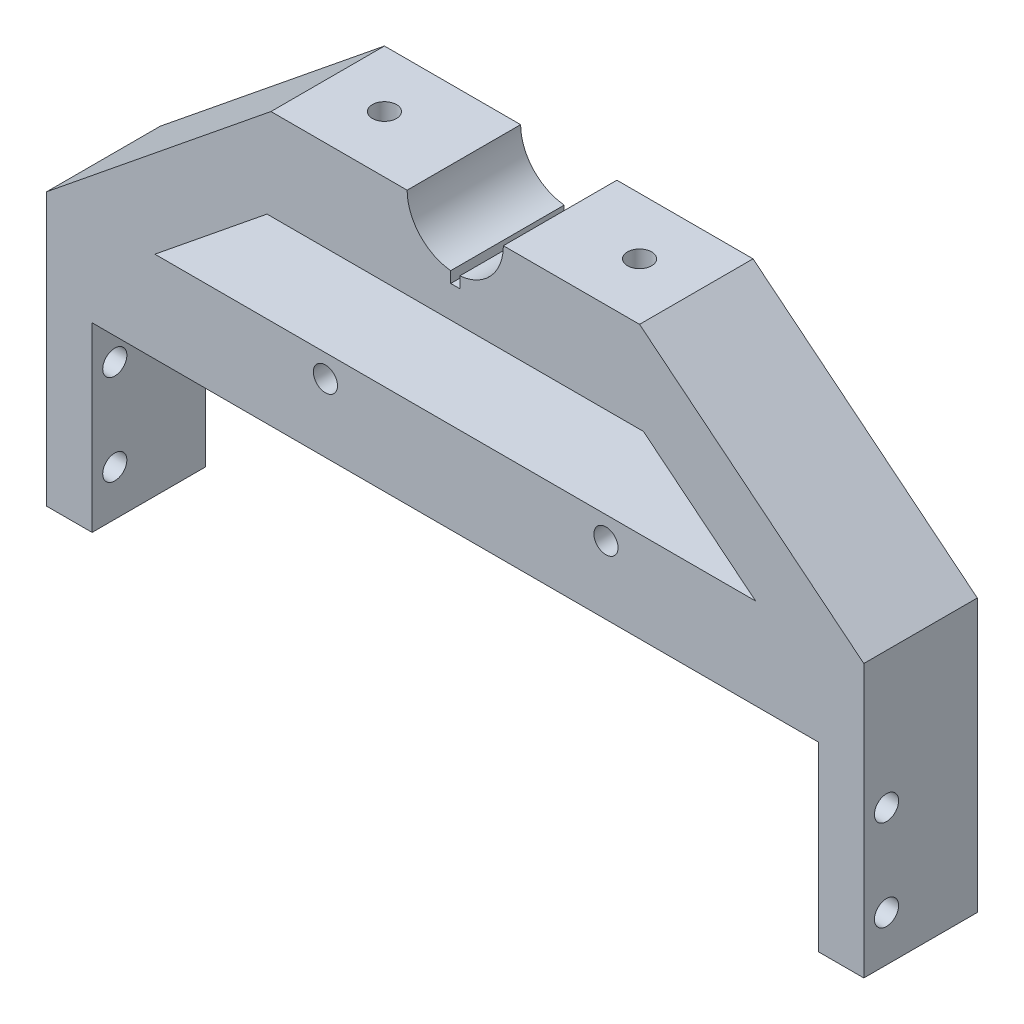
SolidWorks part; units mm, degrees
ref_plane "Front Plane" through (0, 0, 0) normal (0, 0, 1) x (1, 0, 0)
ref_plane "Top Plane" through (0, 0, 0) normal (0, 1, 0) x (1, 0, 0)
ref_plane "Right Plane" through (0, 0, 0) normal (1, 0, 0) x (0, 0, -1)
sketch "Sketch2" plane through (0, 0, 0) normal (0, 0, 1) x (1, 0, 0)
  line L0 (254, 0) -> (266.7, 0)
  line L4 (266.7, 0) -> (266.7, 101.6)
  line L9 (50.8, 0) -> (38.1, 0)
  line L10 (38.1, 0) -> (38.1, 101.6)
  line L12 (38.1, 101.6) -> (100.838, 152.4)
  line L13 (266.7, 101.6) -> (203.962, 152.4)
  line L14 (100.838, 152.4) -> (138.938, 152.4)
  line L15 (165.862, 152.4) -> (203.962, 152.4)
  line L16 (50.8, 0) -> (50.8, 76.2)
  line L17 (50.8, 76.2) -> (254, 76.2)
  line L18 (254, 76.2) -> (254, 0)
  arc A3 (138.938, 152.4) -> (165.862, 152.4) centre (152.4, 152.4) ccw
  dimension "D3" = 12.7
  dimension "D7" = 13.462
  dimension "D2" = 12.7
  dimension "D4" = 228.6
  dimension "D5" = 38.1
  dimension "D8" = 114.3
  dimension "D9" = 38.1
  dimension "D10" = 101.6
  dimension "D11" = 50.8
  dimension "D12" = 76.2
  dimension "D13" = 101.6
  dimension "D14" = 203.2
extrude "Boss-Extrude1" add sketch "Sketch2" along normal blind 50.8
sketch "Sketch3" plane through (38.1, 0, 0) normal (-1, 0, 0) x (0, 0, 1)
  line L2 (50.8, 0) -> (0, 0) construction
  circle A0 centre (25.4, 63.5) radius 3.3782
  circle A1 centre (25.4, 38.1) radius 3.3782
  dimension "D1" = 6.7564
  dimension "D2" = 6.7564
  dimension "D3" = 38.1
  dimension "D4" = 25.4
extrude "Cut-Extrude1" cut sketch "Sketch3" against normal blind 25.4
sketch "Sketch4" plane through (266.7, 0, 0) normal (1, 0, 0) x (0, 0, -1)
  line L1 (-50.8, 0) -> (0, 0) construction
  circle A0 centre (-25.4, 63.5) radius 3.3782
  circle A1 centre (-25.4, 38.1) radius 3.3782
  dimension "D1" = 6.7564
  dimension "D2" = 6.7564
  dimension "D5" = 38.1
  dimension "D6" = 63.5
extrude "Cut-Extrude2" cut sketch "Sketch4" against normal blind 25.4
sketch "Sketch7" plane through (0, 0, 50.8) normal (0, 0, 1) x (1, 0, 0)
  line L1 (12.1672, -21.2745) -> (291.9081, -21.2745)
  line L2 (12.1672, -21.2745) -> (12.1672, 173.6745)
  line L3 (12.1672, 173.6745) -> (291.9081, 173.6745)
  line L4 (291.9081, -21.2745) -> (291.9081, 173.6745)
extrude "Cut-Extrude5" cut sketch "Sketch7" against normal blind 19.05
sketch "Sketch8" plane through (0, 0, 31.75) normal (0, 0, 1) x (1, 0, 0)
  line L0 (38.1, 0) -> (38.1, 101.6) construction
  line L1 (38.1, 25.4) -> (266.7, 25.4)
  line L2 (38.1, 25.4) -> (38.1, 0)
  line L3 (38.1, 0) -> (266.7, 0)
  line L4 (266.7, 25.4) -> (266.7, 0)
  dimension "D1" = 25.4
extrude "Cut-Extrude6" cut sketch "Sketch8" against normal blind 39.37
sketch "Sketch9" plane through (0, 152.4, 0) normal (0, 1, 0) x (1, 0, 0)
  line L1 (138.938, 0) -> (100.838, 0) construction
  line L2 (203.962, 0) -> (165.862, 0) construction
  line L4 (100.838, -31.75) -> (100.838, 0) construction
  line L5 (203.962, -31.75) -> (203.962, 0) construction
  circle A0 centre (116.713, -15.875) radius 3.3782
  circle A1 centre (188.087, -15.875) radius 3.3782
  dimension "D1" = 6.7564
  dimension "D2" = 6.7564
  dimension "D3" = 15.875
  dimension "D4" = 15.875
  dimension "D5" = 15.875
  dimension "D6" = 15.875
extrude "Cut-Extrude7" cut sketch "Sketch9" against normal blind 27.94
sketch "Sketch10" plane through (0, 0, 31.75) normal (0, 0, 1) x (1, 0, 0)
  line L7 (68.3723, 101.6) -> (99.7413, 127)
  line L8 (99.7413, 127) -> (205.0587, 127)
  line L9 (68.3723, 101.6) -> (236.4277, 101.6)
  line L10 (38.1, 101.6) -> (100.838, 152.4) construction
  line L11 (205.0587, 127) -> (236.4277, 101.6)
  line L12 (203.962, 152.4) -> (266.7, 101.6) construction
  dimension "D1" = 25.4
  dimension "D2" = 19.05
  dimension "D3" = 19.05
extrude "Cut-Extrude8" cut sketch "Sketch10" against normal blind 40.64
sketch "Sketch12" plane through (0, 152.4, 0) normal (0, 1, 0) x (1, 0, 0)
  line L0 (152.4, -31.75) -> (152.4, 0)
  line L1 (138.938, -31.75) -> (165.862, -31.75) construction
  line L2 (165.862, 0) -> (138.938, 0) construction
  line L3 (152.4, 0) -> (153.67, 0)
  line L4 (153.67, 0) -> (153.67, -31.75)
  line L5 (153.67, -31.75) -> (151.13, -31.75)
  line L6 (151.13, -31.75) -> (151.13, 0)
  line L7 (151.13, 0) -> (152.4, 0)
  dimension "D1" = 1.27
  dimension "D2" = 1.27
extrude "Cut-Extrude9" cut sketch "Sketch12" against normal blind 16.51 contours L5 L4 L3 L0 | L7 L6 L5 L0 region at (151.765, 152.4, 15.875) region at (153.035, 152.4, 15.875)
sketch "Sketch13" plane through (0, 0, 31.75) normal (0, 0, 1) x (1, 0, 0)
  line L1 (68.3723, 101.6) -> (236.4277, 101.6) construction
  line L2 (38.1, 25.4) -> (38.1, 101.6) construction
  circle A0 centre (116.078, 95.25) radius 3.3782
  circle A1 centre (194.564, 95.25) radius 3.3782
  dimension "D1" = 6.7564
  dimension "D2" = 6.7564
  dimension "D3" = 6.35
  dimension "D4" = 6.35
  dimension "D5" = 77.978
  dimension "D6" = 156.464
extrude "Cut-Extrude10" cut sketch "Sketch13" against normal up to next
